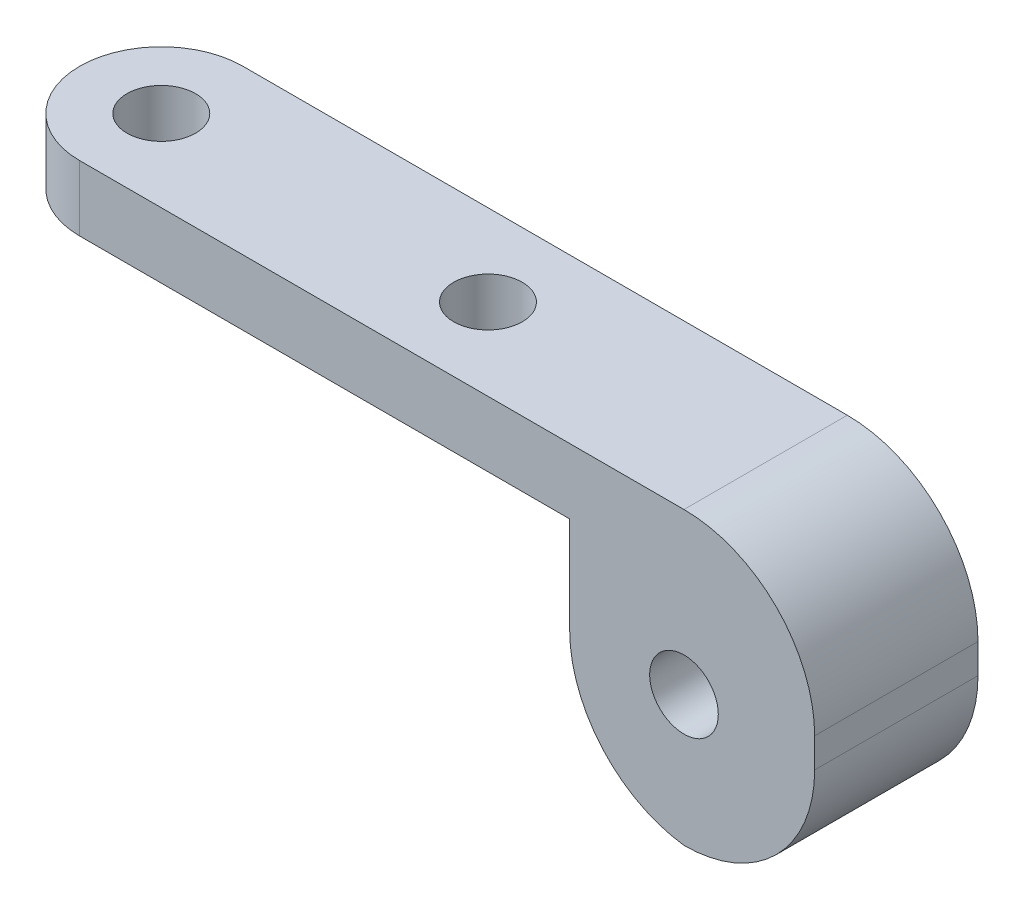
SolidWorks part; units mm, degrees
ref_plane "Front Plane" through (0, 0, 0) normal (0, 0, 1) x (1, 0, 0)
ref_plane "Top Plane" through (0, 0, 0) normal (0, 1, 0) x (1, 0, 0)
ref_plane "Right Plane" through (0, 0, 0) normal (1, 0, 0) x (0, 0, -1)
sketch "Sketch1" plane through (0, 0, 0) normal (0, 1, 0) x (1, 0, 0)
  line L0 (0, 0) -> (20, 0) construction
  line L1 (0, 2.5) -> (20, 2.5)
  line L2 (0, -2.5) -> (20, -2.5)
  arc A0 (0, 2.5) -> (0, -2.5) centre (0, 0) ccw
  arc A1 (20, -2.5) -> (20, 2.5) centre (20, 0) ccw
  circle A2 centre (0, 0) radius 1.05
  circle A3 centre (20, 0) radius 1.05
  point P3 (10, 0)
  dimension "D2" = 2.5
  dimension "D4" = 2.1
  dimension "D5" = 2.1
  dimension "D1" = 20
extrude "Boss-Extrude1" add sketch "Sketch1" along normal blind 2
sketch "Sketch2" plane through (0, 2, 0) normal (0, 1, 0) x (1, 0, 0)
  line L0 (0, 0) -> (10, 0) construction
  line L1 (0, 2.4934) -> (10, 2.4934)
  line L2 (0, -2.4934) -> (10, -2.4934)
  arc A0 (0, 2.4934) -> (0, -2.4934) centre (0, 0) ccw
  arc A1 (10, -2.4934) -> (10, 2.4934) centre (10, 0) ccw
  circle A2 centre (10, 0) radius 1.05
  point P3 (5, 0)
  dimension "D1" = 2.1
  dimension "D2" = 10
extrude "Cut-Extrude1" cut sketch "Sketch2" against normal through all contours A2
sketch "Sketch4" plane through (0, 0, 0) normal (0, -1, 0) x (1, 0, 0)
  line L0 (0, 2.5) -> (20, 2.5) construction
  line L1 (15, 2.5) -> (22.5, 2.5)
  line L2 (15, 2.5) -> (15, -2.5)
  line L3 (15, -2.5) -> (22.5, -2.5)
  line L4 (22.5, 2.5) -> (22.5, -2.5)
  circle A0 centre (20, 0) radius 1.05 construction
  dimension "D1" = 5
  dimension "D2" = 7.5
  dimension "D3" = 5
extrude "Boss-Extrude2" add sketch "Sketch4" along normal blind 6.905 and the other way blind 2
fillet "Fillet1" radius 4 2 edges at (22.5, -6.905, 0) (22.5, 2, 0)
sketch "Sketch5" plane through (0, 0, 2.5) normal (0, 0, 1) x (1, 0, 0)
  circle A0 centre (18.5, -2.905) radius 1.05
  dimension "D1" = 2.1
extrude "Cut-Extrude2" cut sketch "Sketch5" against normal blind 14
fillet "Fillet2" radius 4 1 edges at (15, -6.905, 0)
